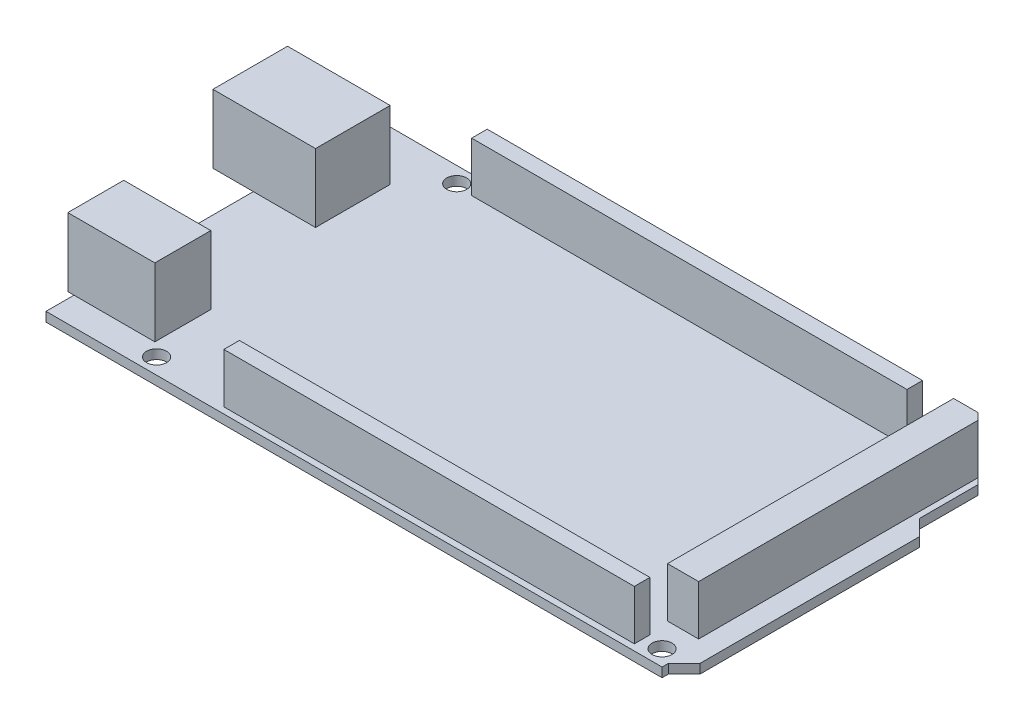
SolidWorks part; units mm, degrees
ref_plane "Front" through (0, 0, 0) normal (0, 0, 1) x (1, 0, 0)
ref_plane "Top" through (0, 0, 0) normal (0, 1, 0) x (1, 0, 0)
ref_plane "Right" through (0, 0, 0) normal (1, 0, 0) x (0, 0, -1)
sketch "Эскиз1" plane through (0, 0, 0) normal (0, 1, 0) x (1, 0, 0)
  line L0 (-22.8897, -15.4977) -> (-22.8897, 37.8423)
  line L1 (-22.8897, 37.8423) -> (73.6303, 37.8423)
  line L2 (73.6303, 37.8423) -> (76.1703, 35.3023)
  line L3 (76.1703, 35.3023) -> (76.1703, 25.9023)
  line L4 (76.1703, 25.9023) -> (78.7103, 23.3623)
  line L5 (78.7103, 23.3623) -> (78.7103, -11.9577)
  line L6 (78.7103, -11.9577) -> (76.1703, -14.4977)
  line L7 (76.1703, -14.4977) -> (76.1703, -15.4977)
  line L8 (76.1703, -15.4977) -> (-22.8897, -15.4977)
  line L10 (-12.8897, 29.8423) -> (-29.3897, 29.8423)
  line L11 (-12.8897, 29.8423) -> (-12.8897, 17.8423)
  line L12 (-12.8897, 17.8423) -> (-29.3897, 17.8423)
  line L13 (-29.3897, 29.8423) -> (-29.3897, 17.8423)
  line L14 (-9.8897, -1.9977) -> (-23.8897, -1.9977)
  line L15 (-9.8897, -1.9977) -> (-9.8897, -10.9977)
  line L16 (-9.8897, -10.9977) -> (-23.8897, -10.9977)
  line L17 (-23.8897, -1.9977) -> (-23.8897, -10.9977)
  line L18 (-4.7897, 37.3423) -> (65.2103, 37.3423)
  line L19 (-4.7897, 37.3423) -> (-4.7897, 34.8423)
  line L20 (-4.7897, 34.8423) -> (65.2103, 34.8423)
  line L21 (65.2103, 37.3423) -> (65.2103, 34.8423)
  line L22 (70.2103, 37.3423) -> (75.2103, 37.3423)
  line L23 (70.2103, 37.3423) -> (70.2103, -8.6577)
  line L24 (70.2103, -8.6577) -> (75.2103, -8.6577)
  line L25 (75.2103, 37.3423) -> (75.2103, -8.6577)
  line L26 (70.7103, -11.9977) -> (4.7103, -11.9977)
  line L27 (70.7103, -11.9977) -> (70.7103, -14.4977)
  line L28 (70.7103, -14.4977) -> (4.7103, -14.4977)
  line L29 (4.7103, -11.9977) -> (4.7103, -14.4977)
  circle A0 centre (-7.6497, 35.3023) radius 1.6
  circle A1 centre (-7.6497, -12.9577) radius 1.6
  circle A2 centre (73.6303, -12.9577) radius 1.6
  circle A3 centre (67.2803, 35.3023) radius 1.6
  dimension "D5" = 3.2
  dimension "D1" = 53.34
  dimension "D2" = 101.6
  dimension "D3" = 74.93
  dimension "D4" = 15.24
  dimension "D6" = 2.54
  dimension "D7" = 9.4
  dimension "D8" = 1
  dimension "D9" = 81.28
  dimension "D10" = 48.26
  dimension "D11" = 2.54
  dimension "D12" = 2.54
  dimension "D13" = 2.54
  dimension "D14" = 2.5
  dimension "D15" = 2.5
  dimension "D16" = 5
  dimension "D17" = 46
  dimension "D18" = 0.5
  dimension "D19" = 0.5
  dimension "D20" = 3.5
  dimension "D21" = 66
  dimension "D22" = 1
  dimension "D23" = 8
  dimension "D24" = 70
  dimension "D25" = 5
  dimension "D26" = 16.5
  dimension "D27" = 12
  dimension "D28" = 10
  dimension "D29" = 8
  dimension "D30" = 14
  dimension "D31" = 9
  dimension "D32" = 4.5
  dimension "D33" = 1
extrude "Бобышка-Вытянуть1" add sketch "Эскиз1" against normal blind 1.5 contours L2 L25 L24 L23 L22 L1 L0 L10 L11 L12 L14 L15 L16 L8 L7 L6 L5 L4 L3 A3 A2 A1 A0 L29 L26 L27 L28 L18 L21 L20 L19 | L16 L15 L14 L0 | L12 L11 L10 L0 | L21 L18 L19 L20 | L26 L29 L28 L27 | L25 L2 L22 L23 L24 region at (27.0658, 0, -10.9282) region at (-16.3897, 0, 6.4977) region at (-17.8897, 0, -23.8423) region at (72.7049, 0, -14.2848) region at (30.2103, 0, -36.0923) region at (37.7103, 0, 13.2477)
extrude "Бобышка-Вытянуть2" add sketch "Эскиз1<3>" along normal blind 8 contours L21 L18 L19 L20 | L25 L2 L22 L23 L24 | L26 L29 L28 L27 region at (72.7049, 0, -14.2848) region at (30.2103, 0, -36.0923) region at (37.7103, 0, 13.2477)
sketch "Эскиз1<3>" plane through (0, 0, 0) normal (0, 1, 0) x (1, 0, 0) same geometry as "Эскиз1"
extrude "Бобышка-Вытянуть3" add sketch "Эскиз1<4>" along normal blind 11 contours L10 L13 L12 L0 | L12 L11 L10 L0 region at (-26.1397, 0, -23.8423) region at (-17.8897, 0, -23.8423)
sketch "Эскиз1<4>" plane through (0, 0, 0) normal (0, 1, 0) x (1, 0, 0) same geometry as "Эскиз1"
extrude "Бобышка-Вытянуть4" add sketch "Эскиз1<5>" along normal blind 11 contours L16 L15 L14 L0 | L14 L17 L16 L0 region at (-23.3897, 0, 6.4977) region at (-16.3897, 0, 6.4977)
sketch "Эскиз1<5>" plane through (0, 0, 0) normal (0, 1, 0) x (1, 0, 0) same geometry as "Эскиз1"
